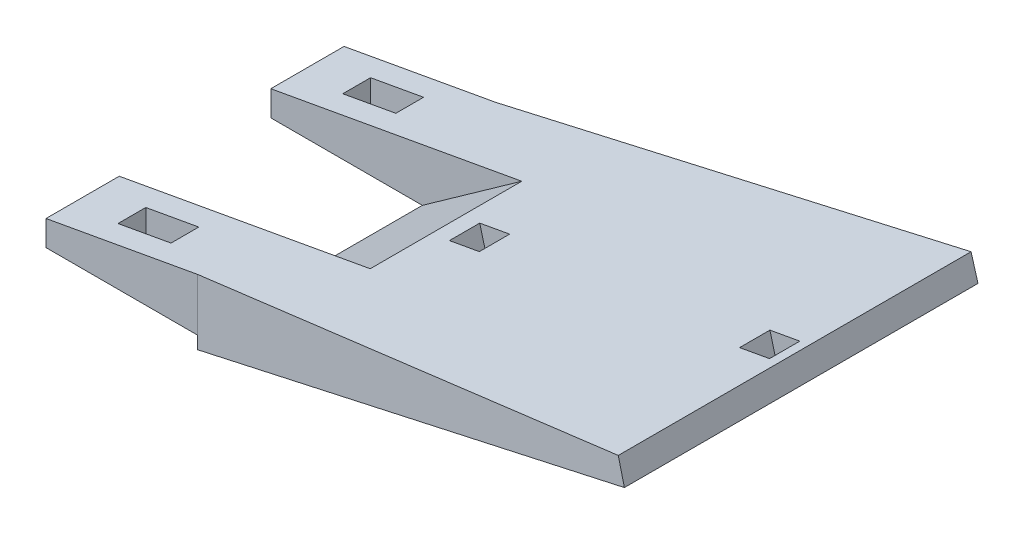
SolidWorks part; units mm, degrees
ref_plane "Alzado" through (0, 0, 0) normal (0, 0, 1) x (1, 0, 0)
ref_plane "Planta" through (0, 0, 0) normal (0, 1, 0) x (1, 0, 0)
ref_plane "Vista lateral" through (0, 0, 0) normal (1, 0, 0) x (0, 0, -1)
sketch "Croquis1" plane through (0, 0, 0) normal (0, 0, 1) x (1, 0, 0)
  line L0 (0, 0) -> (90, 24.1154)
  line L1 (0, 0) -> (0, 2.5)
  line L2 (0, 2.5) -> (-30, 2.5)
  line L3 (-30, 2.5) -> (-30, 7.5)
  line L4 (90, 24.1154) -> (88.7059, 28.9451)
  line L5 (88.7059, 28.9451) -> (-30, 7.5)
  dimension "D1" = 5
  dimension "D2" = 2.5
  dimension "D3" = 30
  dimension "D4" = 90
  dimension "D5" = 5
  dimension "D6" = 75
extrude "Saliente-Extruir1" add sketch "Croquis1" along normal blind 70
sketch "Croquis2" plane through (0, 2.5, 0) normal (0, -1, 0) x (1, 0, 0)
  line L0 (-30, 64.5) -> (-30, 5.5)
  line L1 (-30, 70) -> (-30, 0) construction
  line L2 (0, 70) -> (0, 0) construction
  line L3 (0, 35) -> (-30, 35) construction
  line L4 (-30, 64.5) -> (0, 64.5)
  line L5 (0, 64.5) -> (90, 70)
  line L6 (90, 70) -> (90, 0)
  line L7 (90, 0) -> (0, 5.5)
  line L8 (0, 70) -> (0, 0) construction
  line L9 (0, 5.5) -> (-30, 5.5)
  line L10 (90, 70) -> (-30, 70)
  line L11 (-30, 70) -> (-30, 64.5)
  line L12 (-30, 5.5) -> (-30, 0)
  line L13 (-30, 0) -> (90, 0)
  line L15 (-30, 50) -> (0, 50)
  line L16 (-30, 50) -> (-30, 20)
  line L17 (-30, 20) -> (0, 20)
  line L18 (0, 50) -> (0, 20)
  line L19 (-30, 50) -> (0, 20) construction
  line L20 (-30, 20) -> (0, 50) construction
  line L21 (-20.25, 15.5) -> (-9.75, 15.5)
  line L22 (-20.25, 15.5) -> (-20.25, 10)
  line L23 (-20.25, 10) -> (-9.75, 10)
  line L24 (-9.75, 15.5) -> (-9.75, 10)
  line L25 (-20.25, 15.5) -> (-9.75, 10) construction
  line L26 (-20.25, 10) -> (-9.75, 15.5) construction
  line L27 (-20.25, 60) -> (-9.75, 60)
  line L28 (-20.25, 60) -> (-20.25, 54.5)
  line L29 (-20.25, 54.5) -> (-9.75, 54.5)
  line L30 (-9.75, 60) -> (-9.75, 54.5)
  line L31 (-20.25, 60) -> (-9.75, 54.5) construction
  line L32 (-20.25, 54.5) -> (-9.75, 60) construction
  point P18 (-15, 35)
  point P29 (-15, 12.75)
  point P34 (-15, 57.25)
  line M1 (-30, 0) -> (0, 0)
  line M2 (0, 0) -> (0, 70)
  line M3 (0, 70) -> (-30, 70)
  line M4 (-30, 70) -> (-30, 0)
  dimension "D4" = 7.25
  dimension "D1" = 59
  dimension "D2" = 30
  dimension "D3" = 30
  dimension "D5" = 7.25
  dimension "D6" = 10.5
  dimension "D7" = 5.5
  dimension "D8" = 5.5
  dimension "D9" = 10.5
extrude "Cortar-Extruir1" cut sketch "Croquis2" against normal through all and the other way through all contours L0 L17 L15 M2 | L24 L21 L22 L23 | L9 M2 M4 M1 | L13 L7 M2 | L5 L10 M2 | L4 M4 M2 M3 | L30 L27 L28 L29 region at (-15, 2.5, 67.25) region at (-15, 2.5, 35) region at (30, 2.5, 68.1667) region at (-15, 2.5, 2.75) region at (30, 2.5, 1.8333) region at (-15, 2.5, 12.75) region at (-15, 2.5, 57.25)
sketch "Croquis3" plane through (0, 0, 0) normal (0.2588, -0.9659, 0) x (0.9659, 0.2588, 0)
  line L0 (0, 64.5) -> (0, 5.5) construction
  line L1 (93.1749, 70) -> (93.1749, 0) construction
  line L2 (0, 35) -> (93.1749, 35) construction
  line L4 (27, 38) -> (33, 38)
  line L5 (27, 38) -> (27, 32)
  line L6 (27, 32) -> (33, 32)
  line L7 (33, 38) -> (33, 32)
  line L8 (27, 38) -> (33, 32) construction
  line L9 (27, 32) -> (33, 38) construction
  line L10 (85.1749, 38) -> (91.1749, 38)
  line L11 (85.1749, 38) -> (85.1749, 32)
  line L12 (85.1749, 32) -> (91.1749, 32)
  line L13 (91.1749, 38) -> (91.1749, 32)
  line L14 (85.1749, 38) -> (91.1749, 32) construction
  line L15 (85.1749, 32) -> (91.1749, 38) construction
  point P10 (30, 35)
  point P15 (88.1749, 35)
  dimension "D1" = 30
  dimension "D2" = 6
  dimension "D3" = 6
  dimension "D4" = 6
  dimension "D5" = 6
  dimension "D6" = 5
extrude "Cortar-Extruir2" cut sketch "Croquis3" against normal through all
ref_plane "Plano1" through (0, 0, 35) normal (0, 0, 1) x (1, 0, 0)
sketch "Croquis4" plane through (0, 0, 35) normal (0, 0, 1) x (1, 0, 0)
  line L0 (0, 2.5) -> (0, 12.9197)
  line L1 (0, 12.9197) -> (88.7059, 28.9451)
  line L2 (88.7059, 28.9451) -> (90, 24.1154)
  line L3 (90, 24.1154) -> (0, 0)
  line L4 (0, 12.9197) -> (19.6814, 16.4753)
  line L5 (19.6814, 16.4753) -> (0, 2.5)
  dimension "D1" = 20
extrude "Cortar-Extruir3" cut sketch "Croquis4" against normal blind 15 and the other way blind 15 contours L4 L5 L0
equation "\"A_ALETA\"= ( ( ( tan ( \"ANG_ALETA\" ) ) * \"L_ALETA\" ) + \"A_BASE\" )"
equation "\"A_CAJA\"= ( 2 * \"A_BASE\" ) + \"GAP_ALETAS\""
equation "\"L_ALETA\"=90.000000"
equation "\"TAU_ALETA\"= ( \"L_ALETA\" / ( log ( ( \"A_ALETA\" ) + 1 ) ) )"
equation "\"E_ALETA\"=5.5"
equation "\"R_SONDA\"= 2.05"
equation "\"D_SONDA\"=20.000000"
equation "\"L_CAJA\"=25.000000"
equation "\"E_CAJA\"= 2.5"
equation "\"W_CAJA\"= \"A_CAJA\" * \"CONST_CAJA\""
equation "\"W_CONC\"= ( \"W_CAJA\" / \"CONST_CONC\" ) "
equation "\"A_CONC\"= ( \"A_CAJA\" / \"CONST_CONC\" )"
equation "\"L_CONC\"= \"D_SONDA\" - \"OFFSET_CONC\""
equation "\"W_ALETA\"=70.000000"
equation "\"GAP_ALETAS\"=2"
equation "\"R_C_SONDA\"= 0.63"
equation "\"CONST_CONC\"=2.000000"
equation "\"L_DIE\"= 15"
equation "\"L_CI\"= 18"
equation "\"CONST_CAJA\"=2.000000"
equation "\"ANG_ALETA\"=15.000000"
equation "\"TOLERANCIA\"= 0.5"
equation "\"A_BASE\"= ( \"L_DIE\" - \"E_CAJA\" )"
equation "\"OFFSET_CONC\"= ( 2 * \"R_TORNILLO\" )"
equation "\"R_TORNILLO\"=2.600000"
equation "\"D1@Croquis1\"=\"E_CAJA\"*2"
equation "\"D2@Croquis1\"=\"E_CAJA\""
equation "\"D4@Croquis1\"=\"L_ALETA\""
equation "\"D5@Croquis1\"=\"E_CAJA\" *2"
equation "\"D3@Croquis1\"=\"L_CAJA\"+ 2*\"E_CAJA\""
equation "\"D1@Saliente-Extruir1\"=\"W_ALETA\""
equation "\"D1@Croquis2\"=\"W_CAJA\" +  2*\"E_CAJA\""
equation "\"D2@Croquis2\"=\"L_CAJA\"+\"E_CAJA\"*2 "
equation "\"D3@Croquis2\"=\"L_CAJA\" + \"E_CAJA\"*2"
equation "\"D4@Croquis2\"=(\"W_CAJA\"-\"L_CAJA\")/4"
equation "\"D5@Croquis2\"=(\"W_CAJA\"-\"L_CAJA\")/4"
equation "\"D8@Croquis2\"=\"TOLERANCIA\"+5"
equation "\"D9@Croquis2\"=10.00 + \"TOLERANCIA\""
equation "\"D7@Croquis2\"=5.00 + \"TOLERANCIA\""
equation "\"D6@Croquis2\"=\"TOLERANCIA\"+10"
equation "\"D3@Croquis3\"=\"E_ALETA\"+\"TOLERANCIA\""
equation "\"D2@Croquis3\"=\"E_ALETA\"+\"TOLERANCIA\""
equation "\"D4@Croquis3\"=\"E_ALETA\"+\"TOLERANCIA\""
equation "\"D5@Croquis3\"=\"E_ALETA\"+\"TOLERANCIA\""
equation "\"D6@Croquis1\"=90-\"ANG_ALETA\""
equation "\"D1@Cortar-Extruir3\"=(\"L_CAJA\"+\"E_CAJA\"*2)/2"
equation "\"D2@Cortar-Extruir3\"=(\"L_CAJA\"+\"E_CAJA\"*2)/2"
equation "\"ALARGUE\"=15"
